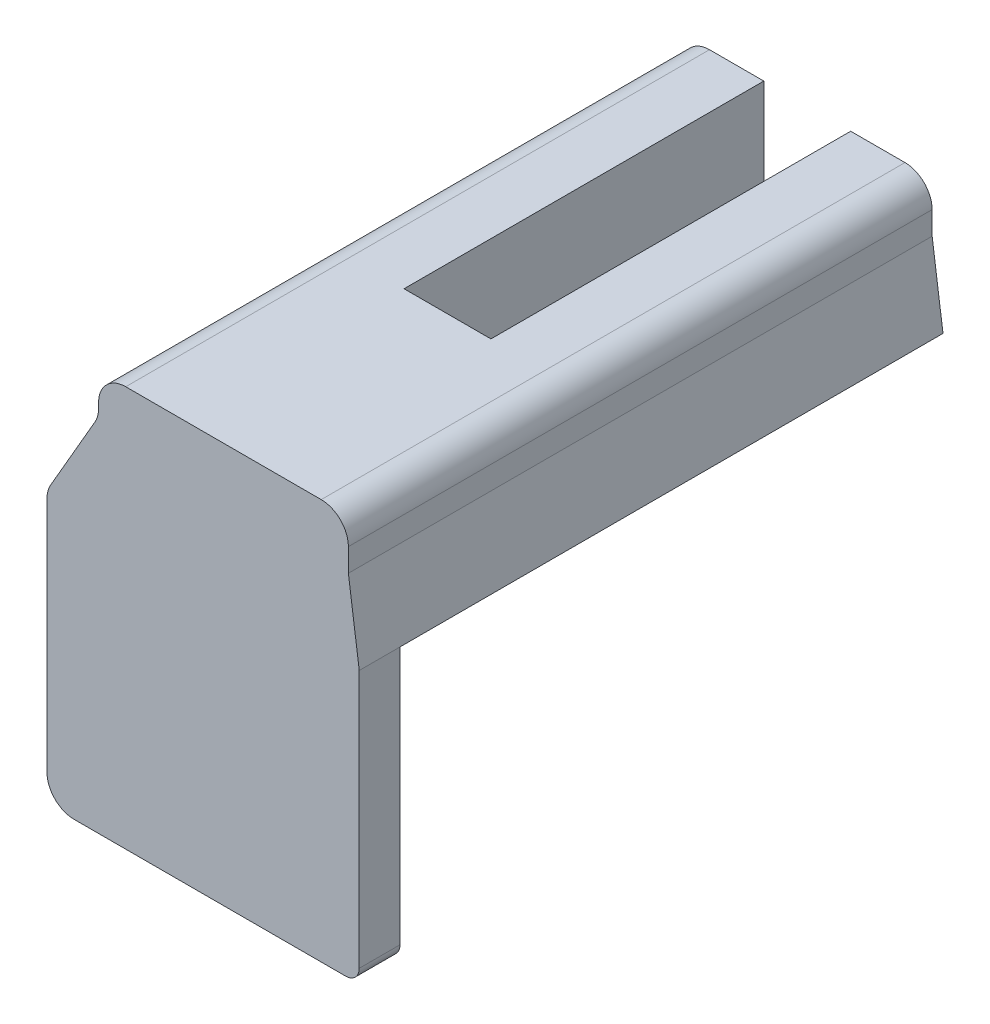
SolidWorks part; units mm, degrees
ref_plane "正面" through (0, 0, 0) normal (0, 0, 1) x (1, 0, 0)
ref_plane "平面" through (0, 0, 0) normal (0, 1, 0) x (1, 0, 0)
ref_plane "右側面" through (0, 0, 0) normal (1, 0, 0) x (0, 0, -1)
sketch "ｽｹｯﾁ1" plane through (0, 0, 0) normal (0, 0, 1) x (1, 0, 0)
  line L1 (-10, 10) -> (10, 10)
  line L2 (-10, 10) -> (-10, -10)
  line L3 (-10, -10) -> (10, -10)
  line L4 (10, 10) -> (10, -10)
  line L5 (-10, 10) -> (10, -10) construction
  line L6 (-10, -10) -> (10, 10) construction
  point P0 (0, 0)
  dimension "D1" = 20
extrude "ﾎﾞｽ - 押し出し1" add sketch "ｽｹｯﾁ1" along normal blind 3
sketch "ｽｹｯﾁ2" plane through (0, 0, 0) normal (0, 0, -1) x (-1, 0, 0)
  line L0 (-10, 10) -> (10, 10) construction
  line L1 (-3, 4) -> (3, 4)
  line L2 (-3, 4) -> (-3, 10)
  line L3 (-3, 10) -> (3, 10)
  line L4 (3, 4) -> (3, 10)
  line L5 (-3, 4) -> (3, 10) construction
  line L6 (-3, 10) -> (3, 4) construction
  line L7 (0, 0) -> (0, 7) construction
  point P0 (0, 7)
  dimension "D1" = 6
  dimension "D2" = 6
extrude "ﾎﾞｽ - 押し出し2" add sketch "ｽｹｯﾁ2" along normal blind 40
sketch "ｽｹｯﾁ3" plane through (0, 0, 3) normal (0, 0, 1) x (1, 0, 0)
  line L5 (-10, -10) -> (10, -10) construction
  line L6 (-10, 10) -> (-13, 10)
  line L7 (-10, 10) -> (-10, -10)
  line L8 (-10, -10) -> (-13, -10)
  line L9 (-13, 10) -> (-13, -10)
  dimension "D1" = 3
extrude "ﾎﾞｽ - 押し出し3" add sketch "ｽｹｯﾁ3" against normal blind 25
sketch "ｽｹｯﾁ4" plane through (-13, 0, 0) normal (1, 0, 0) x (0, 0, -1)
  line L0 (0, 0) -> (22, 0) construction
  circle A0 centre (10, 0) radius 2.6
  dimension "D1" = 10
  dimension "D2" = 5.2
extrude "ｶｯﾄ - 押し出し1" cut sketch "ｽｹｯﾁ4" along normal up to next
fillet "ﾌｨﾚｯﾄ1" radius 1 1 edges at (10, -10, 1.5)
ref_plane "平面1" through (0, 0, -13.5) normal (0, 0, -1) x (-1, 0, 0)
sketch "ｽｹｯﾁ5" plane through (0, 0, -13.5) normal (0, 0, -1) x (-1, 0, 0)
  line L0 (3, 10) -> (-3, 10) construction
  line L1 (-1.6, 6.1) -> (1.6, 6.1)
  line L2 (-1.6, 6.1) -> (-1.6, 10)
  line L3 (-1.6, 10) -> (1.6, 10)
  line L4 (1.6, 6.1) -> (1.6, 10)
  line L5 (-1.6, 6.1) -> (1.6, 10) construction
  line L6 (-1.6, 10) -> (1.6, 6.1) construction
  line L7 (0, 8.05) -> (0, 0) construction
  point P0 (0, 8.05)
  dimension "D1" = 3.2
  dimension "D2" = 3.9
extrude "ｶｯﾄ - 押し出し2" cut sketch "ｽｹｯﾁ5" along normal blind 30
sketch "ｽｹｯﾁ6" plane through (0, 0, 3) normal (0, 0, 1) x (1, 0, 0)
  line L0 (10, 10) -> (-13, 10) construction
  line L1 (3.2, 10) -> (9.2, 10)
  line L2 (3.2, 10) -> (3.2, 19.5)
  line L3 (3.2, 19.5) -> (9.2, 19.5)
  line L4 (9.2, 10) -> (9.2, 19.5)
  line L5 (0, 0) -> (0, 10) construction
  line L6 (-3.2, 19.5) -> (-9.2, 19.5)
  line L7 (-9.2, 10) -> (-9.2, 19.5)
  line L8 (-3.2, 10) -> (-9.2, 10)
  line L9 (-3.2, 10) -> (-3.2, 19.5)
  dimension "D1" = 6.4
  dimension "D2" = 9.5
  dimension "D3" = 6
extrude "ﾎﾞｽ - 押し出し4" add sketch "ｽｹｯﾁ6" against normal up to surface (43 mm away) up to face at (0, 7.525, -40)
sketch "ｽｹｯﾁ7" plane through (0, 0, 3) normal (0, 0, 1) x (1, 0, 0)
  line L1 (-3.2, 19.5) -> (3.2, 19.5)
  line L2 (-3.2, 19.5) -> (-3.2, 10)
  line L3 (-3.2, 10) -> (3.2, 10)
  line L4 (3.2, 19.5) -> (3.2, 10)
extrude "ﾎﾞｽ - 押し出し5" add sketch "ｽｹｯﾁ7" against normal blind 16.5
sketch "ｽｹｯﾁ8" plane through (0, 0, 3) normal (0, 0, 1) x (1, 0, 0)
  line L4 (-13, 10) -> (-9.2, 10)
  line L5 (-9.2, 10) -> (-9.2, 16.5818)
  line L6 (-9.2, 19.5) -> (-9.2, 10) construction
  line L7 (-9.2, 16.5818) -> (-13, 10)
  dimension "D1" = 60
extrude "ﾎﾞｽ - 押し出し6" add sketch "ｽｹｯﾁ8" against normal up to surface (25 mm away) up to face at (-11.5, 0, -22)
fillet "ﾌｨﾚｯﾄ2" radius 2 5 edges at (9.2, 19.5, -18.5) (-9.2, 19.5, -18.5) (-13, -10, -9.5) (-13, 10, -9.5) (-9.2, 16.5818, -9.5)
sketch "ｽｹｯﾁ10" plane through (0, 0, -40) normal (0, 0, -1) x (-1, 0, 0)
  line L0 (3, 4) -> (3, 10) construction
  line L1 (1.6, 6.1) -> (3, 6.1)
  line L2 (1.6, 6.1) -> (1.6, 8.1)
  line L3 (1.6, 8.1) -> (3, 8.1)
  line L4 (3, 6.1) -> (3, 8.1)
  dimension "D1" = 2
extrude "ｶｯﾄ - 押し出し3" cut sketch "ｽｹｯﾁ10" against normal up to surface (26.5 mm away) up to face at (0, 11.12, -13.5)
fillet "ﾌｨﾚｯﾄ3" radius 0.5 2 edges at (-3, 8.1, -26.75) (-3, 6.1, -26.75)
fillet "ﾌｨﾚｯﾄ4" radius 1 2 edges at (3, 4, -20) (-3, 4, -20)
sketch "ｽｹｯﾁ9" plane through (0, 0, 3) normal (0, 0, 1) x (1, 0, 0)
  line L4 (10, 10) -> (9.2, 10)
  line L5 (9.2, 10) -> (9.2, 15.8)
  line L6 (9.2, 10) -> (9.2, 17.5) construction
  line L7 (9.2, 15.8) -> (10, 10)
  dimension "D1" = 5.8
extrude "ﾎﾞｽ - 押し出し7" add sketch "ｽｹｯﾁ9" against normal up to surface (43 mm away) up to face at (0.0663, 6.1655, -40)
